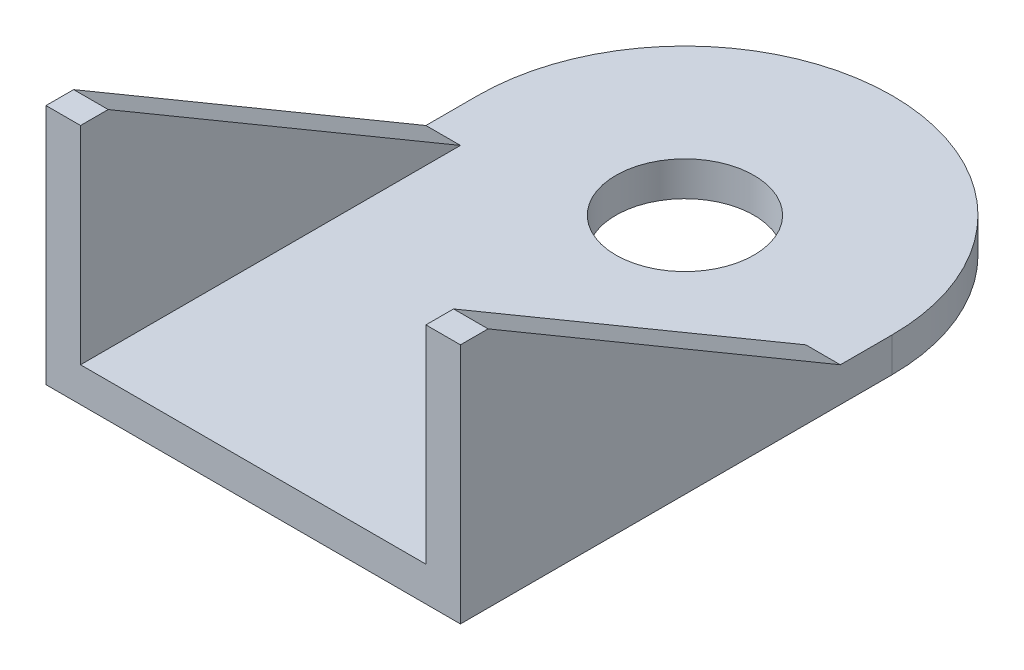
SolidWorks part; units mm, degrees
material "AISI 304"
ref_plane "前视基准面" through (0, 0, 0) normal (0, 0, 1) x (1, 0, 0)
ref_plane "上视基准面" through (0, 0, 0) normal (0, 1, 0) x (1, 0, 0)
ref_plane "右视基准面" through (0, 0, 0) normal (1, 0, 0) x (0, 0, -1)
sketch "草图1" plane through (0, 0, 0) normal (0, 1, 0) x (1, 0, 0)
  line L0 (-12, 0) -> (-12, -25)
  line L1 (-12, -25) -> (12, -25)
  line L2 (12, -25) -> (12, 0)
  circle A0 centre (0, 0) radius 4
  circle A1 centre (0, 0) radius 12
  dimension "D1" = 8
  dimension "D2" = 24
  dimension "D3" = 25
extrude "凸台-拉伸1" add sketch "草图1" along normal blind 2 contours A1 A0 | A1 L0 L1 L2 region at (0, 0, 16.9821) region at (0, 0, -11.6606)
sketch "草图3" plane through (12, 0, 0) normal (1, 0, 0) x (0, 0, -1)
  line L0 (-25, 2) -> (-25, 14)
  line L1 (-25, 14) -> (-23.4, 14)
  line L2 (-23.4, 14) -> (-3, 2)
  line L4 (-25, 2) -> (0, 2) construction
  line L5 (-3, 2) -> (-25, 2)
  dimension "D1" = 1.6
  dimension "D4" = 12
extrude "凸台-拉伸2" add sketch "草图3" against normal blind 2
mirror "镜向1" about plane through (0, 0, 0) normal (1, 0, 0) of "凸台-拉伸2"
ref_plane "基准面1" through (0, 0, 0) normal (0, 0, 1) x (1, 0, 0)
sketch "草图4" [suppressed] plane through (0, 0, 0) normal (0, 0, 1) x (1, 0, 0)
  circle A0 centre (0, 0) radius 41.9162
sketch "草图7" plane through (0, 0, 0) normal (0, -1, 0) x (1, 0, 0)
  circle A0 centre (0, 0) radius 9
split line "分割线1"
sketch "草图8" plane through (0, 0, 0) normal (0, -1, 0) x (1, 0, 0)
  circle A0 centre (0, 0) radius 12
split line "分割线2"
